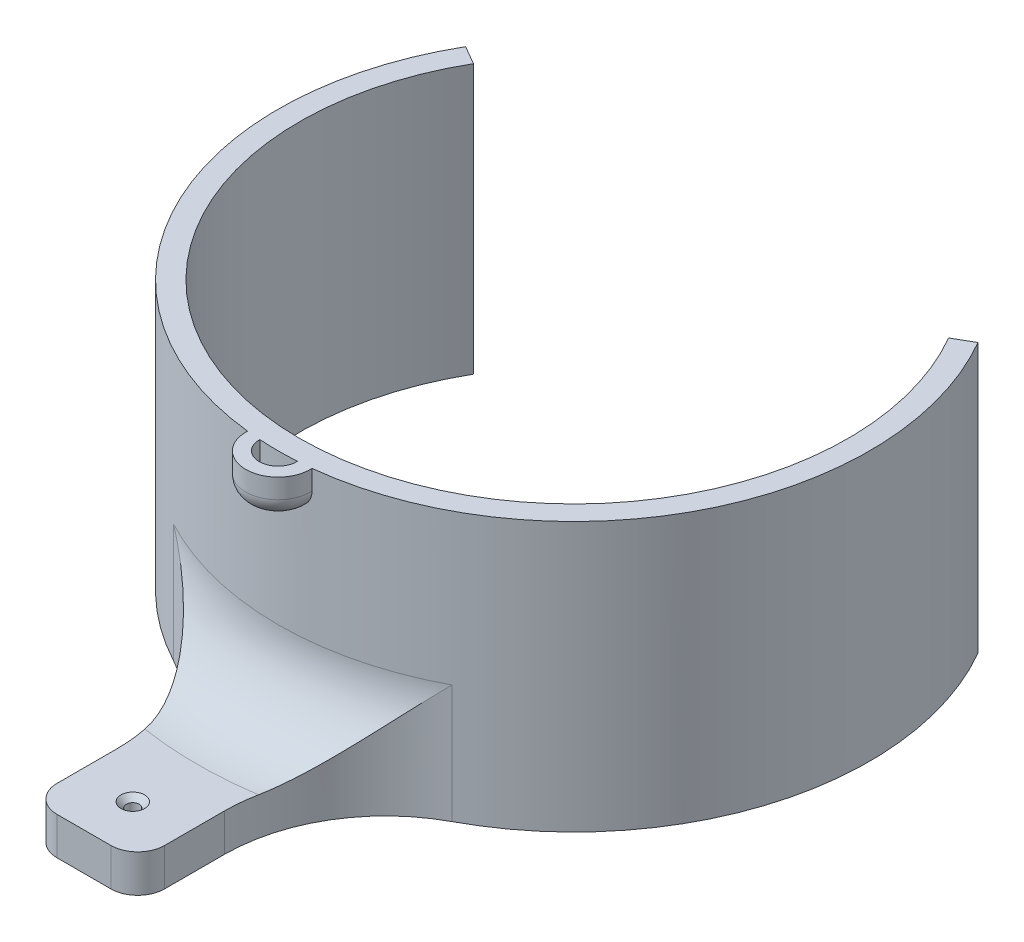
SolidWorks part; units mm, degrees
ref_plane "Piano frontale" through (0, 0, 0) normal (0, 0, 1) x (1, 0, 0)
ref_plane "Piano superiore" through (0, 0, 0) normal (0, 1, 0) x (1, 0, 0)
ref_plane "Piano destro" through (0, 0, 0) normal (1, 0, 0) x (0, 0, -1)
sketch "Schizzo1" plane through (0, 0, 0) normal (0, 1, 0) x (1, 0, 0)
  line L0 (-47.6314, 27.5) -> (-44.1673, 25.5)
  line L1 (44.1673, 25.5) -> (47.6314, 27.5)
  line L2 (0, 0) -> (-44.1673, 25.5) construction
  line L3 (0, 0) -> (44.1673, 25.5) construction
  line L4 (0, 0) -> (0, 51.9167) construction
  line L5 (-10, -54.0833) -> (-10, -86.0833)
  line L6 (-5, -91.0833) -> (5, -91.0833)
  line L7 (10, -86.0833) -> (10, -54.0833)
  line L8 (0, -91.0833) -> (0, 0) construction
  arc A0 (-47.6314, 27.5) -> (47.6314, 27.5) centre (0, 0) ccw
  arc A1 (-44.1673, 25.5) -> (44.1673, 25.5) centre (0, 0) ccw
  arc A3 (10, -86.0833) -> (5, -91.0833) centre (5, -86.0833) cw
  arc A4 (-5, -91.0833) -> (-10, -86.0833) centre (-5, -86.0833) cw
  point P14 (10, -91.0833)
  point P17 (-10, -91.0833)
  dimension "D1" = 110
  dimension "D2" = 4
  dimension "D5" = 20
  dimension "D7" = 5
  dimension "D3" = 120
  dimension "D4" = 60
  dimension "D6" = 37
extrude "Estrusione-Estrusione1" add sketch "Schizzo1" along normal blind 50 contours A1 L1 A0 L0
ref_plane "Piano1" through (0, 0, -27.5) normal (0, 0, 1) x (1, 0, 0)
extrude "Estrusione-Estrusione2" add sketch "Schizzo1<3>" along normal blind 7 contours A0 L5 L6 L7 region at (0, 0, 72.6328)
sketch "Schizzo1<3>" plane through (0, 0, 0) normal (0, 1, 0) x (1, 0, 0) same geometry as "Schizzo1"
sketch "Schizzo2" plane through (0, 7, 0) normal (0, -1, 0) x (1, 0, 0)
  line L1 (0, 82) -> (0, 0) construction
  point P0 (0, 82)
  point P14 (0, 82)
  dimension "D1" = 82
hole_wizard "Foro svasato per Vite M2-1" positions "Schizzo2" profile "Schizzo4" countersink size "M2" standard "ISO"
sketch "Schizzo4" plane through (0, 7, 82) normal (1, 0, 0) x (0, 0, 1)
  line L0 (0, 0) -> (0, 12.661)
  line L1 (0, 12.661) -> (1.2, 11.94)
  line L2 (1.2, 11.94) -> (1.2, 1)
  line L3 (1.2, 1) -> (2.2, 0)
  line L5 (2.2, 0) -> (0, 0)
  line L6 (-1.2, 1) -> (-2.2, 0) construction
  line L10 (0, 12.661) -> (-1.2, 11.94) construction
  line L11 (0, -6.35) -> (0, 107.95) construction
  dimension "Hole Dia." = 2.4
  dimension "Hole Depth" = 11.94
  dimension "Near C'Sink Dia." = 4.4
  dimension "Near C'Sink Angle" = 90
  dimension "Drill Angle" = 118
fillet "Raccordo1" radius 30 2 edges at (10, 3.5, 54.0833) (-10, 3.5, 54.0833)
fillet "Raccordo2" radius 15 1 edges at (0, 7, 55)
sketch "Schizzo5" plane through (0, 50, 0) normal (0, 1, 0) x (1, 0, 0)
  arc A0 (-5.9911, -54.6727) -> (5.9911, -54.6727) centre (0, 0) ccw
  arc A1 (-5.9911, -54.6727) -> (5.9911, -54.6727) centre (0, -55) ccw
  arc A2 (-3.4982, -54.8886) -> (3.4982, -54.8886) centre (0, -55) ccw
  arc A3 (-25.8824, -48.5294) -> (25.8824, -48.5294) centre (0, 0) ccw construction
  arc M4 (-47.6314, 27.5) -> (47.6314, 27.5) centre (0, 0) ccw
  dimension "D1" = 12
  dimension "D2" = 7
extrude "Estrusione-Estrusione3" add sketch "Schizzo5" against normal blind 7 contours A2 A1 M4 region at (-4.7576, 50, 54.93)
fillet "Raccordo3" radius 3.5 1 edges at (0, 43, 61)
